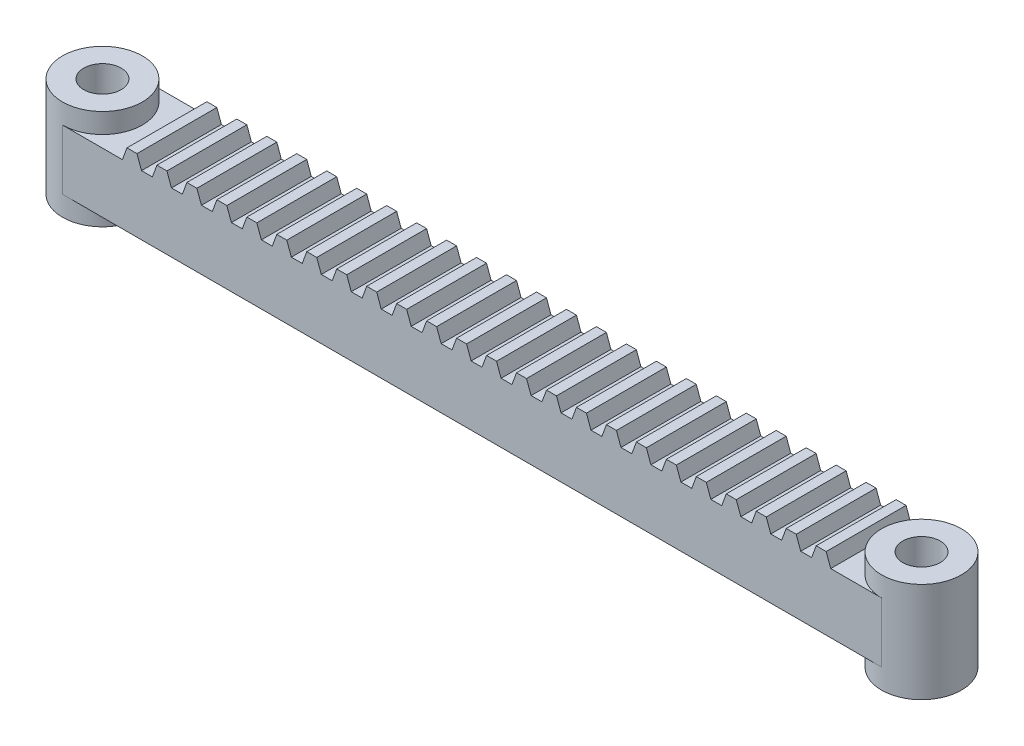
SolidWorks part; units mm, degrees
ref_plane "Front Plane" through (0, 0, 0) normal (0, 0, 1) x (1, 0, 0)
ref_plane "Top Plane" through (0, 0, 0) normal (0, 1, 0) x (1, 0, 0)
ref_plane "Right Plane" through (0, 0, 0) normal (1, 0, 0) x (0, 0, -1)
sketch "Sketch1" plane through (0, 0, 0) normal (0, 1, 0) x (1, 0, 0)
  line L1 (-82, 8) -> (82, 8)
  line L3 (-82, -8) -> (82, -8)
  line L5 (-82, 8) -> (82, -8) construction
  line L6 (-82, -8) -> (82, 8) construction
  circle A0 centre (-82, 0) radius 8
  circle A1 centre (82, 0) radius 8
  circle A2 centre (-82, 0) radius 3.75
  circle A3 centre (82, 0) radius 3.75
  point P0 (0, 0)
  dimension "D3" = 7.5
  dimension "D4" = 7.5
  dimension "D1" = 164
  dimension "D2" = 16
extrude "Boss-Extrude1" add sketch "Sketch1" along normal mid plane 12 contours A1 L1 A0 L3 region at (0, 0, 0)
extrude "Boss-Extrude2" add sketch "Sketch1<3>" along normal mid plane 20 contours A1 A3 | A0 A2 region at (-76.5031, 0, -5.4969) region at (87.4969, 0, -5.4969)
sketch "Sketch1<3>" plane through (0, 0, 0) normal (0, 1, 0) x (1, 0, 0) same geometry as "Sketch1"
sketch "Sketch2" plane through (0, 0, 8) normal (0, 0, 1) x (1, 0, 0)
  line L0 (71.8199, 6) -> (70.9099, 8.5)
  line L1 (-82, 6) -> (82, 6) construction
  line L2 (70.9099, 8.5) -> (68.9099, 8.5)
  line L3 (68.9099, 8.5) -> (68, 6)
  line L4 (68, 6) -> (71.8199, 6)
  line L5 (65.8199, 6) -> (64.9099, 8.5)
  line L7 (64.9099, 8.5) -> (62.9099, 8.5)
  line L8 (62.9099, 8.5) -> (62, 6)
  line L9 (62, 6) -> (65.8199, 6)
  line L10 (59.8199, 6) -> (58.9099, 8.5)
  line L11 (58.9099, 8.5) -> (56.9099, 8.5)
  line L12 (56.9099, 8.5) -> (56, 6)
  line L13 (56, 6) -> (59.8199, 6)
  line L14 (53.8199, 6) -> (52.9099, 8.5)
  line L15 (52.9099, 8.5) -> (50.9099, 8.5)
  line L16 (50.9099, 8.5) -> (50, 6)
  line L17 (50, 6) -> (53.8199, 6)
  line L18 (47.8199, 6) -> (46.9099, 8.5)
  line L19 (46.9099, 8.5) -> (44.9099, 8.5)
  line L20 (44.9099, 8.5) -> (44, 6)
  line L21 (44, 6) -> (47.8199, 6)
  line L22 (41.8199, 6) -> (40.9099, 8.5)
  line L23 (40.9099, 8.5) -> (38.9099, 8.5)
  line L24 (38.9099, 8.5) -> (38, 6)
  line L25 (38, 6) -> (41.8199, 6)
  line L26 (35.8199, 6) -> (34.9099, 8.5)
  line L27 (34.9099, 8.5) -> (32.9099, 8.5)
  line L28 (32.9099, 8.5) -> (32, 6)
  line L29 (32, 6) -> (35.8199, 6)
  line L30 (29.8199, 6) -> (28.9099, 8.5)
  line L31 (28.9099, 8.5) -> (26.9099, 8.5)
  line L32 (26.9099, 8.5) -> (26, 6)
  line L33 (26, 6) -> (29.8199, 6)
  line L34 (23.8199, 6) -> (22.9099, 8.5)
  line L35 (22.9099, 8.5) -> (20.9099, 8.5)
  line L36 (20.9099, 8.5) -> (20, 6)
  line L37 (20, 6) -> (23.8199, 6)
  line L38 (17.8199, 6) -> (16.9099, 8.5)
  line L39 (16.9099, 8.5) -> (14.9099, 8.5)
  line L40 (14.9099, 8.5) -> (14, 6)
  line L41 (14, 6) -> (17.8199, 6)
  line L42 (11.8199, 6) -> (10.9099, 8.5)
  line L43 (10.9099, 8.5) -> (8.9099, 8.5)
  line L44 (8.9099, 8.5) -> (8, 6)
  line L45 (8, 6) -> (11.8199, 6)
  line L46 (5.8199, 6) -> (4.9099, 8.5)
  line L47 (4.9099, 8.5) -> (2.9099, 8.5)
  line L48 (2.9099, 8.5) -> (2, 6)
  line L49 (2, 6) -> (5.8199, 6)
  line L50 (-0.1801, 6) -> (-1.0901, 8.5)
  line L51 (-1.0901, 8.5) -> (-3.0901, 8.5)
  line L52 (-3.0901, 8.5) -> (-4, 6)
  line L53 (-4, 6) -> (-0.1801, 6)
  line L54 (-6.1801, 6) -> (-7.0901, 8.5)
  line L55 (-7.0901, 8.5) -> (-9.0901, 8.5)
  line L56 (-9.0901, 8.5) -> (-10, 6)
  line L57 (-10, 6) -> (-6.1801, 6)
  line L58 (-12.1801, 6) -> (-13.0901, 8.5)
  line L59 (-13.0901, 8.5) -> (-15.0901, 8.5)
  line L60 (-15.0901, 8.5) -> (-16, 6)
  line L61 (-16, 6) -> (-12.1801, 6)
  line L62 (-18.1801, 6) -> (-19.0901, 8.5)
  line L63 (-19.0901, 8.5) -> (-21.0901, 8.5)
  line L64 (-21.0901, 8.5) -> (-22, 6)
  line L65 (-22, 6) -> (-18.1801, 6)
  line L66 (-24.1801, 6) -> (-25.0901, 8.5)
  line L67 (-25.0901, 8.5) -> (-27.0901, 8.5)
  line L68 (-27.0901, 8.5) -> (-28, 6)
  line L69 (-28, 6) -> (-24.1801, 6)
  line L70 (-30.1801, 6) -> (-31.0901, 8.5)
  line L71 (-31.0901, 8.5) -> (-33.0901, 8.5)
  line L72 (-33.0901, 8.5) -> (-34, 6)
  line L73 (-34, 6) -> (-30.1801, 6)
  line L74 (-36.1801, 6) -> (-37.0901, 8.5)
  line L75 (-37.0901, 8.5) -> (-39.0901, 8.5)
  line L76 (-39.0901, 8.5) -> (-40, 6)
  line L77 (-40, 6) -> (-36.1801, 6)
  line L78 (-42.1801, 6) -> (-43.0901, 8.5)
  line L79 (-43.0901, 8.5) -> (-45.0901, 8.5)
  line L80 (-45.0901, 8.5) -> (-46, 6)
  line L81 (-46, 6) -> (-42.1801, 6)
  line L82 (-48.1801, 6) -> (-49.0901, 8.5)
  line L83 (-49.0901, 8.5) -> (-51.0901, 8.5)
  line L84 (-51.0901, 8.5) -> (-52, 6)
  line L85 (-52, 6) -> (-48.1801, 6)
  line L86 (-54.1801, 6) -> (-55.0901, 8.5)
  line L87 (-55.0901, 8.5) -> (-57.0901, 8.5)
  line L88 (-57.0901, 8.5) -> (-58, 6)
  line L89 (-58, 6) -> (-54.1801, 6)
  line L90 (-60.1801, 6) -> (-61.0901, 8.5)
  line L91 (-61.0901, 8.5) -> (-63.0901, 8.5)
  line L92 (-63.0901, 8.5) -> (-64, 6)
  line L93 (-64, 6) -> (-60.1801, 6)
  line L94 (-66.1801, 6) -> (-67.0901, 8.5)
  line L95 (-67.0901, 8.5) -> (-69.0901, 8.5)
  line L96 (-69.0901, 8.5) -> (-70, 6)
  line L97 (-70, 6) -> (-66.1801, 6)
  dimension "D1" = 2
  dimension "D2" = 24
  dimension "D3" = 40
extrude "Boss-Extrude3" add sketch "Sketch2" against normal blind 16
